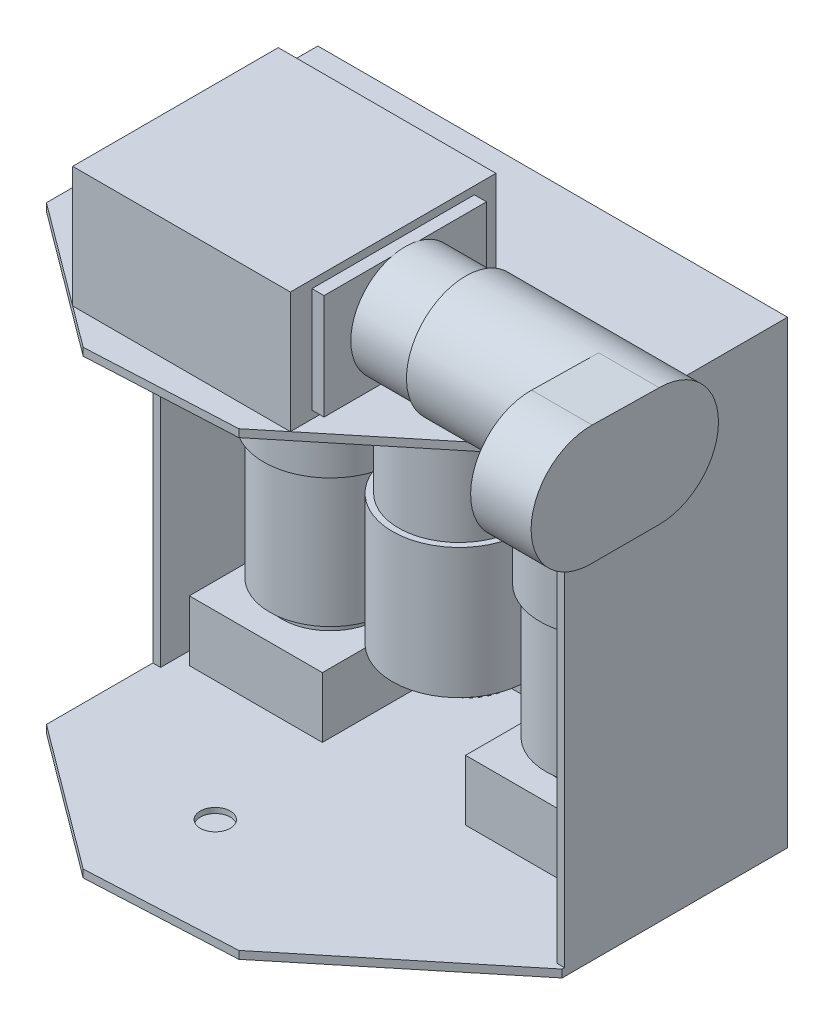
SolidWorks part; units mm, degrees
ref_plane "Front Plane" through (0, 0, 0) normal (0, 0, 1) x (1, 0, 0)
ref_plane "Top Plane" through (0, 0, 0) normal (0, 1, 0) x (1, 0, 0)
ref_plane "Right Plane" through (0, 0, 0) normal (1, 0, 0) x (0, 0, -1)
sketch "Sketch1" plane through (0, 0, 0) normal (0, 1, 0) x (1, 0, 0)
  line L0 (-71.1993, 0) -> (119.8007, 0)
  line L1 (119.8007, 0) -> (119.8007, -90)
  line L2 (119.8007, -90) -> (46.2729, -150.1553)
  line L3 (46.2729, -150.1553) -> (-15.0357, -153.1811)
  line L4 (-15.0357, -153.1811) -> (-74.3993, -109)
  line L5 (-74.3993, -109) -> (-74.3993, -65)
  line L6 (-74.3993, -65) -> (-71.1993, -65)
  line L7 (-71.1993, -65) -> (-71.1993, 0)
  dimension "D1" = 191
  dimension "D2" = 90
  dimension "D3" = 74
  dimension "D4" = 95
  dimension "D6" = 65
  dimension "D7" = 3.2
  dimension "D9" = 44
extrude "Boss-Extrude1" add sketch "Sketch1" along normal blind 3.2
sketch "Sketch3" plane through (0, 0, 0) normal (0, -1, 0) x (1, 0, 0)
  line L1 (-74.3993, 108.0683) -> (119.7657, 108.4369) construction
  line L2 (-74.3993, 65) -> (-74.3993, 109) construction
  line L3 (-5.3993, 152.7055) -> (-5.3993, 0) construction
  line L4 (-15.0357, 153.1811) -> (46.2729, 150.1553) construction
  line L5 (119.8007, 0) -> (-71.1993, 0) construction
  circle A0 centre (-5.3993, 108.1993) radius 12.3
  dimension "D3" = 24.6
  dimension "D1" = 45
  dimension "D2" = 69
extrude "Boss-Extrude2" add sketch "Sketch3" along normal blind 3.2
sketch "Sketch4" plane through (0, -3.2, 0) normal (0, -1, 0) x (1, 0, 0)
  circle A0 centre (-5.3993, 108.1993) radius 4
  dimension "D1" = 8
extrude "Boss-Extrude3" add sketch "Sketch4" along normal blind 4
sketch "Sketch6" plane through (0, 0, 0) normal (0, 1, 0) x (1, 0, 0)
  line L0 (-74.3993, -65) -> (-74.3993, 0)
  line L1 (-74.3993, 0) -> (-71.1993, 0)
  line L2 (-71.1993, 0) -> (-71.1993, -65)
  line L3 (-71.1993, -65) -> (-74.3993, -65)
extrude "Boss-Extrude4" add sketch "Sketch6" along normal blind 190
sketch "Sketch8" plane through (0, 0, 0) normal (0, 1, 0) x (1, 0, 0)
  line L0 (119.8007, 0) -> (116.6007, 0)
  line L1 (119.8007, 0) -> (-71.1993, 0) construction
  line L2 (116.6007, 0) -> (116.6007, -89)
  line L3 (116.6007, -89) -> (119.8007, -89)
  line L4 (119.8007, -90) -> (119.8007, 0) construction
  line L5 (119.8007, -89) -> (119.8007, 0)
  dimension "D1" = 3.2
  dimension "D2" = 89
extrude "Boss-Extrude5" add sketch "Sketch8" along normal blind 190
ref_plane "Plane2" through (0, 95, 0) normal (0, -1, 0) x (-1, 0, 0)
mirror "Mirror1" about plane through (0, 95, 0) normal (0, -1, 0) of "Boss-Extrude3", "Boss-Extrude1", "Boss-Extrude2"
sketch "Sketch9" plane through (0, 0, 0) normal (0, 0, 1) x (1, 0, 0)
  line L0 (22.7007, 190) -> (22.7007, 0) construction
  line L3 (-74.3993, 95) -> (119.8007, 95) construction
  line L4 (-74.3993, 186.8) -> (-74.3993, 3.2) construction
  line L5 (119.8007, 186.8) -> (119.8007, 3.2) construction
  line L6 (119.8007, 190) -> (-74.3993, 190) construction
  line L7 (119.8007, 0) -> (-74.3993, 0) construction
  line L8 (119.8007, 190) -> (119.8007, 0) construction
  line L9 (-74.3993, 0) -> (119.8007, 0)
  line L10 (-74.3993, 0) -> (-74.3993, 190)
  line L11 (-74.3993, 190) -> (119.8007, 190)
  line L12 (119.8007, 0) -> (119.8007, 190)
  line L13 (-74.3993, 0) -> (119.8007, 190) construction
  line L14 (-74.3993, 190) -> (119.8007, 0) construction
  point P12 (22.7007, 95)
extrude "Boss-Extrude7" add sketch "Sketch9" against normal blind 3.2
sketch "Sketch10" plane through (0, 3.2, 0) normal (0, 1, 0) x (1, 0, 0)
  circle A0 centre (-5.3993, -108.1993) radius 6.2
  dimension "D1" = 12.4
ref_plane "Plane3" through (0, 95, 0) normal (0, 1, 0) x (1, 0, 0)
sketch "Sketch11" plane through (0, 95, 0) normal (0, 1, 0) x (1, 0, 0)
  circle A0 centre (-5.3993, -108.1993) radius 6.2
extrude "Cut-Extrude2" cut sketch "Sketch11" against normal mid plane 188
sketch "Sketch12" plane through (0, 0, -3.2) normal (0, 0, -1) x (-1, 0, 0)
  line L0 (-22.7007, 190) -> (-22.7007, 0) construction
  line L1 (-119.8007, 190) -> (74.3993, 190) construction
  line L2 (74.3993, 0) -> (-119.8007, 0) construction
  line L3 (-119.8007, 95) -> (74.3993, 95) construction
  line L4 (-119.8007, 0) -> (-119.8007, 190) construction
  line L5 (74.3993, 190) -> (74.3993, 0) construction
  circle A0 centre (-22.7007, 95) radius 35
  dimension "D1" = 70
extrude "Boss-Extrude8" add sketch "Sketch12" along normal blind 20
sketch "Sketch14" plane through (0, 190, 0) normal (0, 1, 0) x (1, 0, 0)
  line L0 (-31.9964, -140.5581) -> (58.0036, -140.5581)
  line L1 (-74.3993, -109) -> (-15.0357, -153.1811) construction
  line L2 (46.2729, -150.1553) -> (119.8007, -90) construction
  line L3 (58.0036, -140.5581) -> (58.0036, -55.5581)
  line L4 (58.0036, -55.5581) -> (-31.9964, -55.5581)
  line L5 (-31.9964, -55.5581) -> (-31.9964, -140.5581)
  dimension "D1" = 90
  dimension "D2" = 85
extrude "Boss-Extrude9" add sketch "Sketch14" along normal blind 50
sketch "Sketch19" plane through (58.0036, 0, 0) normal (1, 0, 0) x (0, 0, -1)
  line L0 (-140.5581, 215) -> (-55.5581, 215) construction
  line L1 (-140.5581, 240) -> (-140.5581, 190) construction
  line L2 (-55.5581, 240) -> (-55.5581, 190) construction
  line L3 (-98.0581, 240) -> (-98.0581, 190) construction
  line L4 (-140.5581, 240) -> (-55.5581, 240) construction
  line L5 (-140.5581, 190) -> (-55.5581, 190) construction
  line L7 (-64.4732, 193.2455) -> (-131.6431, 193.2455)
  line L8 (-64.4732, 193.2455) -> (-64.4732, 236.7545)
  line L9 (-64.4732, 236.7545) -> (-131.6431, 236.7545)
  line L10 (-131.6431, 193.2455) -> (-131.6431, 236.7545)
  line L11 (-64.4732, 193.2455) -> (-131.6431, 236.7545) construction
  line L12 (-64.4732, 236.7545) -> (-131.6431, 193.2455) construction
  point P12 (-98.0581, 215)
extrude "Boss-Extrude11" add sketch "Sketch19" along normal blind 5
sketch "Sketch20" plane through (63.0036, 0, 0) normal (1, 0, 0) x (0, 0, -1)
  line L0 (-131.6431, 215) -> (-64.4732, 215) construction
  line L1 (-131.6431, 236.7545) -> (-131.6431, 193.2455) construction
  line L2 (-64.4732, 193.2455) -> (-64.4732, 236.7545) construction
  line L3 (-98.0581, 236.7545) -> (-98.0581, 193.2455) construction
  line L4 (-64.4732, 236.7545) -> (-131.6431, 236.7545) construction
  line L5 (-131.6431, 193.2455) -> (-64.4732, 193.2455) construction
  circle A0 centre (-98.0581, 215) radius 22.5
  dimension "D1" = 45
extrude "Boss-Extrude12" add sketch "Sketch20" along normal blind 25
sketch "Sketch21" plane through (88.0036, 0, 0) normal (1, 0, 0) x (0, 0, -1)
  circle A0 centre (-98.0581, 215) radius 24.4875
extrude "Boss-Extrude13" add sketch "Sketch21" along normal blind 55
sketch "Sketch22" plane through (143.0036, 0, 0) normal (1, 0, 0) x (0, 0, -1)
  line L0 (-98.0581, 239.4875) -> (-125.8268, 240)
  line L1 (-140.5581, 240) -> (-55.5581, 240) construction
  line L2 (-126.7402, 190.5125) -> (-98.0581, 190.5125)
  circle A0 centre (-98.0581, 215) radius 24.4875 construction
  arc A1 (-125.8268, 240) -> (-126.7402, 190.5125) centre (-126.2835, 215.2563) ccw
  arc A2 (-98.0581, 190.5125) -> (-98.0581, 239.4875) centre (-98.0581, 215) ccw
extrude "Boss-Extrude14" add sketch "Sketch22" along normal blind 25
ref_plane "Plane4" through (0, 7.2, 0) normal (0, 1, 0) x (1, 0, 0)
sketch "Sketch25" plane through (0, 7.2, 0) normal (0, 1, 0) x (1, 0, 0)
  line L0 (-34.3993, 3.2) -> (-34.3993, -154.9603) construction
  line L1 (-74.3993, 3.2) -> (119.8007, 3.2) construction
  line L2 (79.8007, 3.2) -> (79.8007, -154.9603) construction
  line L3 (-74.3993, 3.2) -> (-74.3993, -109) construction
  line L4 (119.8007, -90) -> (119.8007, 3.2) construction
  line L5 (22.7007, 3.2) -> (22.7007, -157.682) construction
  line L6 (57.7007, 3.2) -> (-12.2993, 3.2) construction
  line L7 (-74.3993, -31.6695) -> (119.8007, -31.6695) construction
  line L9 (-6.8993, -0.9149) -> (-61.8993, -0.9149)
  line L10 (-6.8993, -0.9149) -> (-6.8993, -62.4242)
  line L11 (-6.8993, -62.4242) -> (-61.8993, -62.4242)
  line L12 (-61.8993, -0.9149) -> (-61.8993, -62.4242)
  line L13 (-6.8993, -0.9149) -> (-61.8993, -62.4242) construction
  line L14 (-6.8993, -62.4242) -> (-61.8993, -0.9149) construction
  line L15 (107.3007, -0.9149) -> (52.3007, -0.9149)
  line L16 (107.3007, -0.9149) -> (107.3007, -62.4242)
  line L17 (107.3007, -62.4242) -> (52.3007, -62.4242)
  line L18 (52.3007, -0.9149) -> (52.3007, -62.4242)
  line L19 (107.3007, -0.9149) -> (52.3007, -62.4242) construction
  line L20 (107.3007, -62.4242) -> (52.3007, -0.9149) construction
  point P16 (-34.3993, -31.6695)
  point P21 (79.8007, -31.6695)
  dimension "D1" = 40
  dimension "D2" = 40
  dimension "D3" = 55
  dimension "D4" = 55
extrude "Boss-Extrude16" add sketch "Sketch25" along normal blind 25 separate body
sketch "Sketch26" plane through (0, 32.2, 0) normal (0, 1, 0) x (1, 0, 0)
  line L0 (79.8007, -0.9149) -> (79.8007, -62.4242) construction
  line L1 (107.3007, -0.9149) -> (52.3007, -0.9149) construction
  line L2 (52.3007, -62.4242) -> (107.3007, -62.4242) construction
  line L3 (52.3007, -31.6695) -> (107.3007, -31.6695) construction
  line L4 (52.3007, -0.9149) -> (52.3007, -62.4242) construction
  line L5 (107.3007, -62.4242) -> (107.3007, -0.9149) construction
  circle A0 centre (79.8007, -31.6695) radius 20
  dimension "D1" = 40
extrude "Boss-Extrude17" add sketch "Sketch26" along normal blind 5
sketch "Sketch27" plane through (0, 37.2, 0) normal (0, 1, 0) x (1, 0, 0)
  line L0 (79.8007, -11.6695) -> (79.8007, -51.6695) construction
  line L1 (59.8007, -31.6695) -> (99.8007, -31.6695) construction
  circle A0 centre (79.8007, -31.6695) radius 20 construction
  circle A1 centre (79.8007, -31.6695) radius 25
  dimension "D1" = 50
extrude "Boss-Extrude18" add sketch "Sketch27" along normal blind 55
sketch "Sketch28" plane through (0, 92.2, 0) normal (0, 1, 0) x (1, 0, 0)
  circle A0 centre (79.8007, -31.6695) radius 27.5
  dimension "D1" = 55
extrude "Boss-Extrude19" add sketch "Sketch28" along normal blind 53.8
sketch "Sketch29" plane through (0, 146, 0) normal (0, 1, 0) x (1, 0, 0)
  circle A0 centre (79.8007, -31.6695) radius 10
  dimension "D1" = 20
extrude "Boss-Extrude20" add sketch "Sketch29" along normal blind 4
sketch "Sketch30" plane through (0, 150, 0) normal (0, 1, 0) x (1, 0, 0)
  circle A0 centre (79.8007, -31.6695) radius 17.5
  dimension "D1" = 35
extrude "Boss-Extrude21" add sketch "Sketch30" along normal blind 5
sketch "Sketch31" plane through (0, 155, 0) normal (0, 1, 0) x (1, 0, 0)
  line L0 (79.8007, -31.6695) -> (62.3007, -31.6695) construction
  line L1 (79.8007, -31.6695) -> (79.8007, -13.2912) construction
  line L2 (62.5279, -34.4806) -> (64.5071, -33.1152)
  line L3 (64.2766, -30.2509) -> (62.4506, -29.3838)
  circle A0 centre (79.8007, -31.6695) radius 17.5 construction
  arc A1 (64.5071, -33.1152) -> (64.2766, -30.2509) centre (63.5649, -31.7496) ccw
  arc A2 (62.5279, -34.4806) -> (62.4506, -29.3838) centre (79.8007, -31.6695) cw
  dimension "D1" = 60
extrude "Cut-Extrude4" cut sketch "Sketch31" against normal blind 5
pattern_circular "CirPattern1" count 21 every 17 about axis through (79.8007, 155, 31.6695) along (0, 1, 0) of "Cut-Extrude4"
ref_plane "Plane5" through (22.7007, 0, 0) normal (-1, 0, 0) x (0, 0, 1)
mirror "Mirror2" about plane through (22.7007, 0, 0) normal (-1, 0, 0) of "CirPattern1", "Cut-Extrude4", "Boss-Extrude21", "Boss-Extrude20", "Boss-Extrude19", "Boss-Extrude18", "Boss-Extrude17"
sketch "Sketch32" plane through (0, 186.8, 0) normal (0, -1, 0) x (1, 0, 0)
  line L0 (22.7007, -3.2) -> (22.7007, 151.3187) construction
  line L1 (-12.2993, -3.2) -> (57.7007, -3.2) construction
  line L2 (-15.0357, 153.1811) -> (46.2729, 150.1553) construction
  line L3 (-74.3993, 35.8129) -> (119.8007, 35.8129) construction
  line L4 (-74.3993, -3.2) -> (-74.3993, 109) construction
  line L5 (119.8007, 90) -> (119.8007, -3.2) construction
  line L7 (52.7007, 8.3129) -> (-7.2993, 8.3129)
  line L8 (52.7007, 8.3129) -> (52.7007, 63.3129)
  line L9 (52.7007, 63.3129) -> (-7.2993, 63.3129)
  line L10 (-7.2993, 8.3129) -> (-7.2993, 63.3129)
  line L11 (52.7007, 8.3129) -> (-7.2993, 63.3129) construction
  line L12 (52.7007, 63.3129) -> (-7.2993, 8.3129) construction
  point P12 (22.7007, 35.8129)
  dimension "D1" = 60
  dimension "D2" = 55
extrude "Boss-Extrude22" add sketch "Sketch32" along normal blind 29
sketch "Sketch33" plane through (0, 157.8, 0) normal (0, -1, 0) x (1, 0, 0)
  line L0 (22.7007, 63.3129) -> (22.7007, 7.7051) construction
  line L1 (52.7007, 63.3129) -> (-7.2993, 63.3129) construction
  line L2 (-7.2993, 35.8129) -> (53.4627, 35.8129) construction
  line L3 (-7.2993, 63.3129) -> (-7.2993, 8.3129) construction
  circle A0 centre (22.7007, 35.509) radius 20
  dimension "D1" = 40
extrude "Boss-Extrude23" add sketch "Sketch33" along normal blind 5
sketch "Sketch34" plane through (0, 152.8, 0) normal (0, -1, 0) x (1, 0, 0)
  circle A0 centre (22.7007, 35.509) radius 25
  dimension "D1" = 50
extrude "Boss-Extrude24" add sketch "Sketch34" along normal blind 55
sketch "Sketch35" plane through (0, 97.8, 0) normal (0, -1, 0) x (1, 0, 0)
  circle A0 centre (22.7007, 35.509) radius 27.5
  dimension "D1" = 55
extrude "Boss-Extrude25" add sketch "Sketch35" along normal blind 53.8
sketch "Sketch36" plane through (0, 44, 0) normal (0, -1, 0) x (1, 0, 0)
  circle A0 centre (22.7007, 35.509) radius 10
  dimension "D1" = 20
extrude "Boss-Extrude26" add sketch "Sketch36" along normal blind 4
sketch "Sketch37" plane through (0, 40, 0) normal (0, -1, 0) x (1, 0, 0)
  circle A0 centre (22.7007, 31.8019) radius 17.5
  dimension "D1" = 35
extrude "Boss-Extrude27" add sketch "Sketch37" along normal blind 5
sketch "Sketch38" plane through (0, 35, 0) normal (0, -1, 0) x (1, 0, 0)
  line L0 (22.7007, 49.3019) -> (22.7007, 11.4355) construction
  line L1 (5.2007, 31.8019) -> (40.2007, 31.8019) construction
  line L6 (20.8801, 49.0533) -> (21.1794, 46.2176)
  line L7 (22.7007, 46.3782) -> (23.3115, 49.1761)
  circle A0 centre (22.7007, 31.8019) radius 17.5 construction
  arc A5 (21.1794, 46.2176) -> (22.7007, 46.3782) centre (21.94, 46.2979) ccw
  arc A6 (20.8801, 49.0533) -> (23.3115, 49.1761) centre (22.2287, 46.4829) cw
extrude "Cut-Extrude5" cut sketch "Sketch38" against normal blind 5
pattern_circular "CirPattern2" count 40 over 360 about axis through (22.7007, 35, 31.8019) along (0, -1, 0) of "Cut-Extrude5"
